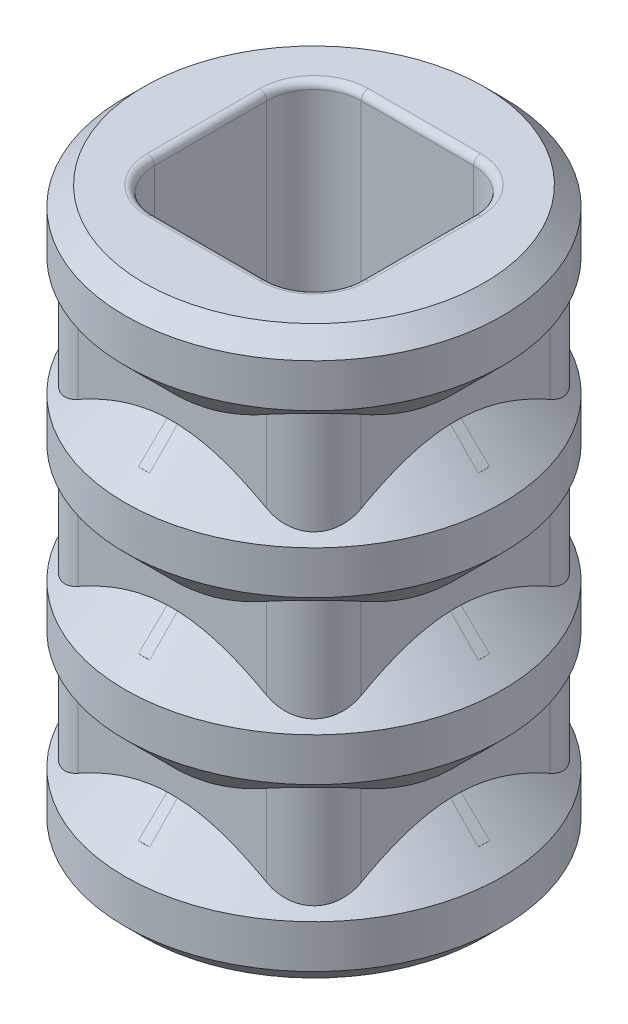
SolidWorks part; units mm, degrees
ref_plane "Front Plane" through (0, 0, 0) normal (0, 0, 1) x (1, 0, 0)
ref_plane "Top Plane" through (0, 0, 0) normal (0, 1, 0) x (1, 0, 0)
ref_plane "Right Plane" through (0, 0, 0) normal (1, 0, 0) x (0, 0, -1)
sketch "Sketch1" plane through (0, 0, 0) normal (0, 1, 0) x (1, 0, 0)
  line L1 (-5.95, -10.95) -> (5.95, -10.95)
  line L2 (-10.95, -5.95) -> (-10.95, 5.95)
  line L3 (-5.95, 10.95) -> (5.95, 10.95)
  line L4 (10.95, -5.95) -> (10.95, 5.95)
  line L5 (-10.95, -10.95) -> (10.95, 10.95) construction
  line L6 (-10.95, 10.95) -> (10.95, -10.95) construction
  line L11 (-10, -15) -> (10, -15)
  line L12 (-15, -10) -> (-15, 10)
  line L13 (-10, 15) -> (10, 15)
  line L14 (15, -10) -> (15, 10)
  line L15 (-15, -15) -> (15, 15) construction
  line L16 (-15, 15) -> (15, -15) construction
  arc A0 (-5.95, -10.95) -> (-10.95, -5.95) centre (-5.95, -5.95) cw
  arc A1 (5.95, -10.95) -> (10.95, -5.95) centre (5.95, -5.95) ccw
  arc A2 (5.95, 10.95) -> (10.95, 5.95) centre (5.95, 5.95) cw
  arc A3 (-10.95, 5.95) -> (-5.95, 10.95) centre (-5.95, 5.95) cw
  arc A8 (-10, -15) -> (-15, -10) centre (-10, -10) cw
  arc A9 (10, -15) -> (15, -10) centre (10, -10) ccw
  arc A10 (10, 15) -> (15, 10) centre (10, 10) cw
  arc A11 (-15, 10) -> (-10, 15) centre (-10, 10) cw
  point P0 (0, 0)
  point P18 (0, 0)
  point P19 (0, 0)
  dimension "D3" = 5
  dimension "D6" = 5
  dimension "D1" = 21.9
  dimension "D2" = 21.9
  dimension "D4" = 30
  dimension "D5" = 30
extrude "Boss-Extrude1" add sketch "Sketch1" along normal blind 60
sketch "Sketch4" plane through (0, 0, 0) normal (0, 0, 1) x (1, 0, 0)
  line L0 (-10.95, 0) -> (-20, 0)
  line L1 (-20, 0) -> (-20, 8.57)
  line L2 (-20, 8.57) -> (-15, 8.57)
  line L3 (-15, 8.57) -> (-15, 17.14)
  line L4 (-15, 17.14) -> (-20, 17.14)
  line L5 (-20, 17.14) -> (-20, 25.71)
  line L6 (-20, 25.71) -> (-15, 25.71)
  line L7 (-15, 25.71) -> (-15, 34.28)
  line L8 (-15, 34.28) -> (-20, 34.28)
  line L9 (-20, 34.28) -> (-20, 42.85)
  line L10 (-20, 42.85) -> (-15, 42.85)
  line L11 (-15, 42.85) -> (-15, 51.42)
  line L12 (-15, 51.42) -> (-20, 51.42)
  line L13 (-20, 51.42) -> (-20, 60)
  line L14 (-20, 60) -> (-15, 60)
  line L15 (-15, 0) -> (-15, 60)
  line L16 (0, -5.1019) -> (0, 65.7026) construction
  line L17 (-10, 60) -> (-15, 60) construction
  line L18 (-15, 60) -> (-15, 0) construction
  dimension "D2" = 5
  dimension "D3" = 8.57
  dimension "D1" = 5
revolve "Revolve1" add sketch "Sketch4" angle 360 about L16 region at (-17.5, 55.71, 0) region at (-17.5, 38.565, 0) region at (-17.5, 21.425, 0) region at (-17.5, 4.285, 0)
chamfer "Chamfer1" distance 2 angle 45 8 edges at (0, 0, -20) (0, 8.57, -20) (0, 17.14, -20) (0, 25.71, -20) (0, 51.42, -20) (0, 60, -20) (0, 42.85, -20) (0, 34.28, -20)
fillet "Fillet1" radius 0.75 16 edges at (-9.4855, 0, -9.4855) (0, 0, -10.95) (9.4855, 0, -9.4855) (10.95, 0, 0) (9.4855, 0, 9.4855) (0, 0, 10.95) (-9.4855, 0, 9.4855) (9.4855, 60, -9.4855) (10.95, 60, 0) (9.4855, 60, 9.4855) (0, 60, 10.95) (-9.4855, 60, 9.4855) (-10.95, 60, 0) (-9.4855, 60, -9.4855) (-10.95, 0, 0) (0, 60, -10.95)
chamfer "Chamfer2" distance 2.99 angle 45 24 edges at (-15, 34.28, 0) (0, 34.28, 15) (0, 17.14, 15) (0, 25.71, 15) (0, 8.57, 15) (15, 17.14, 0) (15, 34.28, 0) (15, 25.71, 0) (15, 8.57, 0) (0, 17.14, -15) (-15, 17.14, 0) (0, 8.57, -15) (-15, 8.57, 0) (0, 25.71, -15) (-15, 25.71, 0) (-15, 42.85, 0) (-15, 51.42, 0) (0, 51.42, 15) (0, 42.85, 15) (15, 42.85, 0) (15, 51.42, 0) (0, 51.42, -15) (0, 42.85, -15) (0, 34.28, -15)
equation "\"D2@Sketch1\"=\"D1@Sketch1\""
equation "\"D5@Sketch1\"=\"D4@Sketch1\""
equation "\"D2@Sketch4\"=\"D1@Sketch4\""
